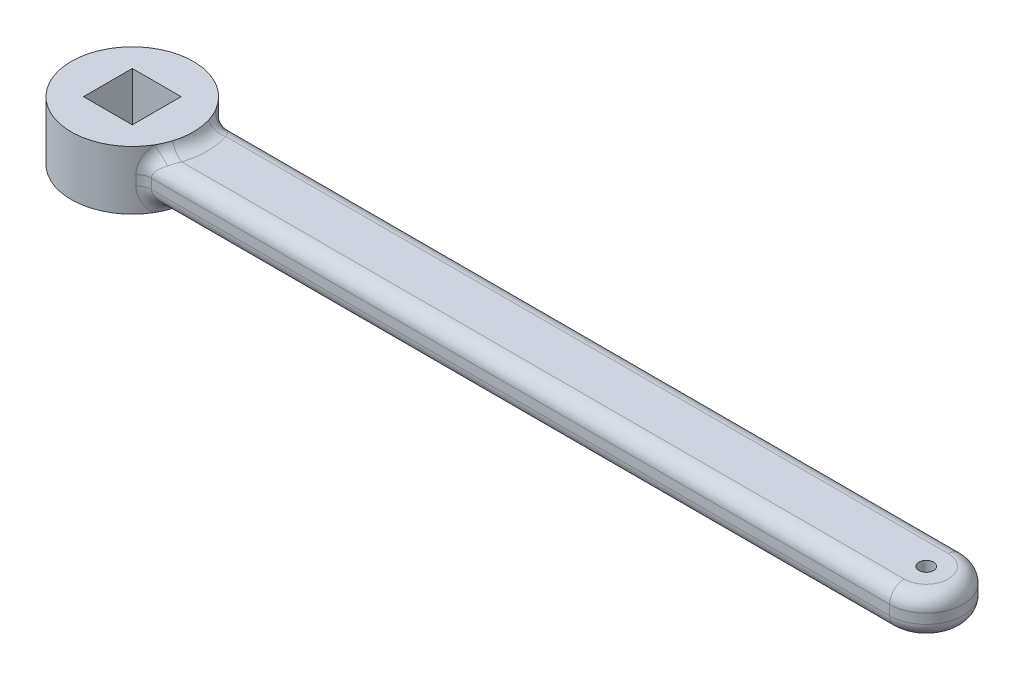
SolidWorks part; units mm, degrees
ref_plane "Спереди" through (0, 0, 0) normal (0, 0, 1) x (1, 0, 0)
ref_plane "Сверху" through (0, 0, 0) normal (0, 1, 0) x (1, 0, 0)
ref_plane "Справа" through (0, 0, 0) normal (1, 0, 0) x (0, 0, -1)
other "Configuration Table"
sketch "Эскиз1" plane through (0, 0, 0) normal (0, 1, 0) x (1, 0, 0)
  circle A0 centre (0, 0) radius 12.5
  dimension "D1" = 25
extrude "Бобышка-Вытянуть1" add sketch "Эскиз1" along normal mid plane 12
sketch "Эскиз2" plane through (0, 0, 0) normal (0, 1, 0) x (1, 0, 0)
  line L0 (0, 0) -> (162.5, 0) construction
  line L1 (0, 7.5) -> (162.5, 7.5)
  line L2 (0, -7.5) -> (162.5, -7.5)
  arc A0 (0, 7.5) -> (0, -7.5) centre (0, 0) ccw
  arc A1 (162.5, -7.5) -> (162.5, 7.5) centre (162.5, 0) ccw
  circle A2 centre (162.5, 0) radius 1.5
  point P4 (81.25, 0)
  dimension "D3" = 3
  dimension "D1" = 15
  dimension "D2" = 162.5
extrude "Бобышка-Вытянуть2" add sketch "Эскиз2" along normal mid plane 8
sketch "Эскиз3" plane through (0, 6, 0) normal (0, 1, 0) x (1, 0, 0)
  line L1 (5, -5) -> (-5, -5)
  line L2 (5, -5) -> (5, 5)
  line L3 (5, 5) -> (-5, 5)
  line L4 (-5, -5) -> (-5, 5)
  line L5 (0, 5) -> (0, -5) construction
  line L6 (5, 0) -> (-5, 0) construction
  point P0 (0, 0)
  dimension "D1" = 10
extrude "Вырез-Вытянуть1" cut sketch "Эскиз3" against normal through all
fillet "Скругление5" radius 3 6 edges at (86.25, 4, 7.5) (170, 4, 0) (86.25, -4, 7.5) (170, -4, 0) (86.25, 4, -7.5) (86.25, -4, -7.5)
fillet "Скругление6" radius 3 6 edges at (10.6881, -3.2522, 6.4818) (10, 0, 7.5) (10.3421, 2.6266, 7.0207) (10.6881, 3.2522, -6.4818) (10, 0, -7.5) (10.3421, -2.6266, -7.0207)
